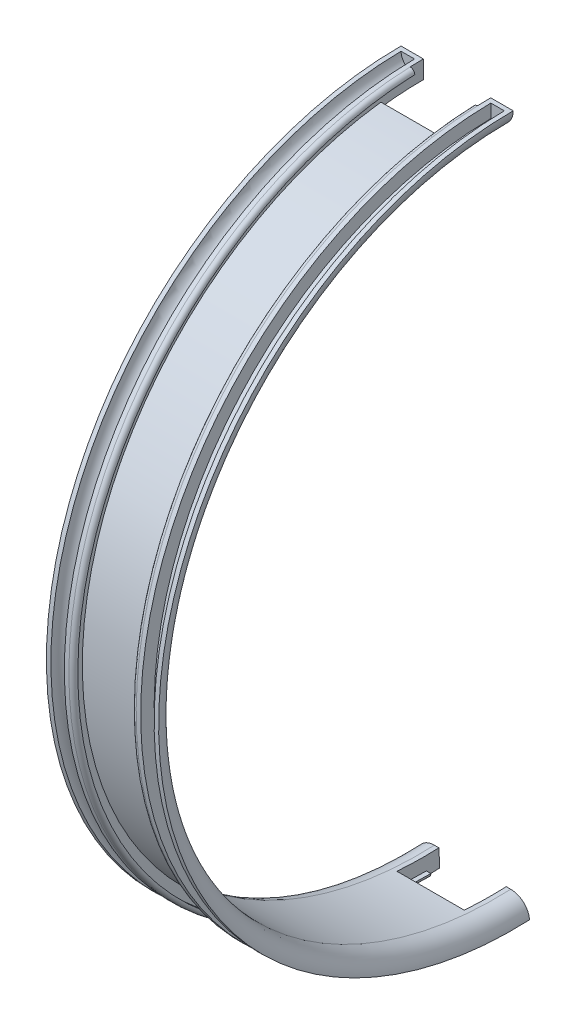
SolidWorks part; units mm, degrees
ref_plane "Alzado" through (0, 0, 0) normal (0, 0, 1) x (1, 0, 0)
ref_plane "Planta" through (0, 0, 0) normal (0, 1, 0) x (1, 0, 0)
ref_plane "Vista lateral" through (0, 0, 0) normal (1, 0, 0) x (0, 0, -1)
sketch "Croquis1" plane through (0, 0, 0) normal (0, 0, 1) x (1, 0, 0)
  line L0 (8.5728, 10.5114) -> (3.5728, 10.5114)
  line L1 (-16.4272, 10.5114) -> (8.5728, 10.5114)
  line L2 (-16.4272, 10.5114) -> (-16.4272, 6.5114)
  line L3 (-16.4272, 6.5114) -> (8.5728, 6.5114)
  line L4 (8.5728, 10.5114) -> (8.5728, 6.5114)
  line L5 (-16.4272, 6.5114) -> (8.5728, 6.5114)
  line L6 (-16.4272, 6.5114) -> (-16.4272, 7.5114)
  line L7 (-16.4272, 7.5114) -> (8.5728, 7.5114)
  line L8 (8.5728, 6.5114) -> (8.5728, 7.5114)
  line L9 (-16.4272, 10.5114) -> (-15.4272, 10.5114)
  line L10 (-16.4272, 10.5114) -> (-16.4272, 6.5114)
  line L11 (-16.4272, 6.5114) -> (-15.4272, 6.5114)
  line L12 (-15.4272, 10.5114) -> (-15.4272, 6.5114)
  line L13 (8.5728, 10.5114) -> (7.5728, 10.5114)
  line L14 (8.5728, 10.5114) -> (8.5728, 6.5114)
  line L15 (8.5728, 6.5114) -> (7.5728, 6.5114)
  line L16 (7.5728, 10.5114) -> (7.5728, 6.5114)
  line L17 (-16.4272, 10.5114) -> (-11.4272, 10.5114)
  line L18 (-12.4272, 10.5114) -> (-12.4272, -68.4886)
  line L19 (-11.4272, 10.5114) -> (-12.4272, 10.5114)
  line L20 (-11.4272, 10.5114) -> (-11.4272, 6.5114)
  line L21 (-11.4272, 6.5114) -> (-12.4272, 6.5114)
  line L22 (-12.4272, 10.5114) -> (-12.4272, 6.5114)
  line L23 (3.5728, 10.5114) -> (4.5728, 10.5114)
  line L24 (3.5728, 10.5114) -> (3.5728, 6.5114)
  line L25 (3.5728, 6.5114) -> (4.5728, 6.5114)
  line L26 (4.5728, 10.5114) -> (4.5728, 6.5114)
  line L27 (-11.4272, 10.5114) -> (-10.4272, 10.5114)
  line L28 (-11.4272, 10.5114) -> (-11.4272, 9.5114)
  line L29 (-11.4272, 9.5114) -> (-10.4272, 9.5114)
  line L30 (-10.4272, 10.5114) -> (-10.4272, 9.5114)
  line L31 (3.5728, 10.5114) -> (2.5728, 10.5114)
  line L32 (3.5728, 10.5114) -> (3.5728, 9.5114)
  line L33 (3.5728, 9.5114) -> (2.5728, 9.5114)
  line L34 (2.5728, 10.5114) -> (2.5728, 9.5114)
  line L35 (-12.4272, -68.4886) -> (67.7698, -68.4886)
  circle A0 centre (4.5728, 10.5114) radius 4
  circle A1 centre (4.5728, 10.5114) radius 3
  circle A2 centre (-12.4272, 10.5114) radius 4
  circle A3 centre (-12.4272, 10.5114) radius 3
  circle A4 centre (-11.4272, 9.5114) radius 1
  circle A5 centre (3.5728, 9.5114) radius 1
  dimension "D1" = 25
  dimension "D2" = 4
  dimension "D3" = 1
  dimension "D4" = 1
  dimension "D5" = 1
  dimension "D6" = 5
  dimension "D7" = 5
  dimension "D8" = 1
  dimension "D9" = 1
  dimension "D10" = 1
  dimension "D11" = 1
  dimension "D12" = 1
  dimension "D13" = 1
  dimension "D14" = 79
revolve "Revolución1" add sketch "Croquis1" angle 182.63 about L35 region at (7.9774, 9.5004, 0) region at (6.8849, 8.1994, 0) region at (4.3494, 10.2881, 0) region at (4.0838, 7.0317, 0) region at (4.1363, 8.1674, 0) region at (5.5839, 7.1068, 0) region at (3.8213, 7.5626, 0) region at (-3.9272, 6.9883, 0) region at (2.977, 7.1909, 0) region at (3.9972, 9.5114, 0) region at (3.1484, 9.9358, 0) region at (3.822, 6.5494, 0) region at (-15.8318, 9.5004, 0) region at (-10.8314, 7.1909, 0) region at (-14.7393, 8.1994, 0) region at (-11.9907, 8.1674, 0) region at (-11.6758, 7.5626, 0) region at (-11.9382, 7.0317, 0) region at (-11.6764, 6.5494, 0) region at (-12.2038, 10.2881, 0) region at (-11.0028, 9.9358, 0) region at (-11.8516, 9.5114, 0) region at (-13.4383, 7.1068, 0)
sketch "Croquis2" plane through (0, 0, 0) normal (0, 0, -1) x (-1, 0, 0)
  line L0 (-4.5728, 7.5114) -> (-4.5728, 10.5114)
  line L1 (-4.5728, 10.5114) -> (-7.5728, 10.5114)
  line L2 (12.4272, 7.5114) -> (12.4272, 10.5114)
  line L3 (12.4272, 10.5114) -> (15.4272, 10.5114)
  line L4 (11.4272, 10.5114) -> (11.4272, -68.4886)
  line L5 (11.4272, -68.4886) -> (39.6484, -68.4886)
  circle A0 centre (-4.5728, 10.5114) radius 3
  circle A1 centre (12.4272, 10.5114) radius 3
  arc A2 (11.4272, 10.5114) -> (10.4272, 9.5114) centre (11.4272, 9.5114) ccw construction
  dimension "D1" = 79
revolve "Revolución2" add sketch "Croquis2" angle 0.72 about L5 region at (5.846, 9.2382, 0) region at (-13.7005, 9.2382, 0) reverse direction yes
sketch "Croquis3" plane through (0, -0.1442, 3.1397) normal (0, 0.0459, -0.9989) x (-1, 0, 0)
  line L0 (15.4272, -147.4164) -> (-7.5728, -147.4164)
  line L1 (3.9272, -147.4164) -> (3.9272, -68.4164)
  line L2 (3.9272, -68.4164) -> (85.2148, -68.4164)
  circle A0 centre (-4.5728, -147.4164) radius 3
  circle A1 centre (12.4272, -147.4164) radius 3
  dimension "D1" = 79
revolve "Revolución3" add sketch "Croquis3" angle 0.72 about L2 region at (-13.7005, -146.1334, -3.5669) region at (5.846, -146.1334, -3.5669)
sketch "Croquis4" plane through (0, 0, 0) normal (0, 0, -1) x (-1, 0, 0)
  line L0 (12.4272, 6.5114) -> (-4.5728, 6.5114) construction
  line L1 (-3.5728, 6.5114) -> (11.4272, 6.5114)
  line L2 (-3.5728, 6.5114) -> (-3.5728, 7.5114)
  line L3 (-3.5728, 7.5114) -> (11.4272, 7.5114)
  line L4 (11.4272, 6.5114) -> (11.4272, 7.5114)
  line L5 (-3.5728, 10.5114) -> (-3.5728, -68.4886)
  line L6 (-3.5728, -68.4886) -> (1.7395, -68.4886)
  dimension "D1" = 79
revolve "Cortar-Revolución3" cut sketch "Croquis4" angle 7.16 about L6 region at (-3.9272, 7.0114, 0) reverse direction yes
sketch "Croquis5" plane through (0, -0.1442, 3.1397) normal (0, 0.0459, -0.9989) x (-1, 0, 0)
  line L0 (12.4272, -143.4164) -> (-4.5728, -143.4164) construction
  line L1 (-3.5728, -144.4164) -> (11.4272, -144.4164)
  line L2 (-3.5728, -144.4164) -> (-3.5728, -143.4164)
  line L3 (-3.5728, -143.4164) -> (11.4272, -143.4164)
  line L4 (11.4272, -144.4164) -> (11.4272, -143.4164)
  line L5 (-3.5728, -147.4164) -> (-3.5728, -68.4164)
  line L6 (-3.5728, -68.4164) -> (15.9024, -68.4164)
  dimension "D1" = 79
revolve "Cortar-Revolución4" cut sketch "Croquis5" angle 7.16 about L6
sketch "Croquis6" plane through (0, -0.1442, 3.1397) normal (0, 0.0459, -0.9989) x (-1, 0, 0)
  line L0 (-3.5728, -147.4164) -> (-3.5728, -68.4164)
  line L1 (-3.5728, -146.4164) -> (-1.6795, -146.4164)
  line L2 (-3.5728, -146.4164) -> (-3.5728, -148.2442)
  line L3 (-3.5728, -148.2442) -> (-1.6795, -148.2442)
  line L4 (-1.6795, -146.4164) -> (-1.6795, -148.2442)
  line L5 (11.4272, -146.4164) -> (9.5533, -146.4164)
  line L6 (11.4272, -146.4164) -> (11.4272, -148.2442)
  line L7 (11.4272, -148.2442) -> (9.5533, -148.2442)
  line L8 (9.5533, -146.4164) -> (9.5533, -148.2442)
  line L9 (-3.5728, -68.4164) -> (32.9155, -68.4164)
  dimension "D1" = 79
revolve "Cortar-Revolución5" cut sketch "Croquis6" angle 2.15 about L9 region at (3.1484, -146.8304, -3.5989) region at (-10.4903, -147.3193, -3.6214)
sketch "Croquis7" plane through (0, 0, 0) normal (0, 0, -1) x (-1, 0, 0)
  line L0 (-3.5728, 10.5114) -> (-3.5728, -68.4886)
  line L1 (-3.5728, 9.5114) -> (-0.1872, 9.5114)
  line L2 (-3.5728, 9.5114) -> (-3.5728, 11.1783)
  line L3 (-3.5728, 11.1783) -> (-0.1872, 11.1783)
  line L4 (-0.1872, 9.5114) -> (-0.1872, 11.1783)
  line L5 (11.4272, 9.5114) -> (8.8019, 9.5114)
  line L6 (11.4272, 9.5114) -> (11.4272, 10.8925)
  line L7 (11.4272, 10.8925) -> (8.8019, 10.8925)
  line L8 (8.8019, 9.5114) -> (8.8019, 10.8925)
  line L9 (-3.5728, -68.4886) -> (11.4272, -68.4886)
  dimension "D1" = 79
revolve "Cortar-Revolución6" cut sketch "Croquis7" angle 2.15 about L9 region at (3.1484, 9.9358, 0) region at (1.6749, 10.411, 0) region at (-10.1145, 10.202, 0) reverse direction yes
